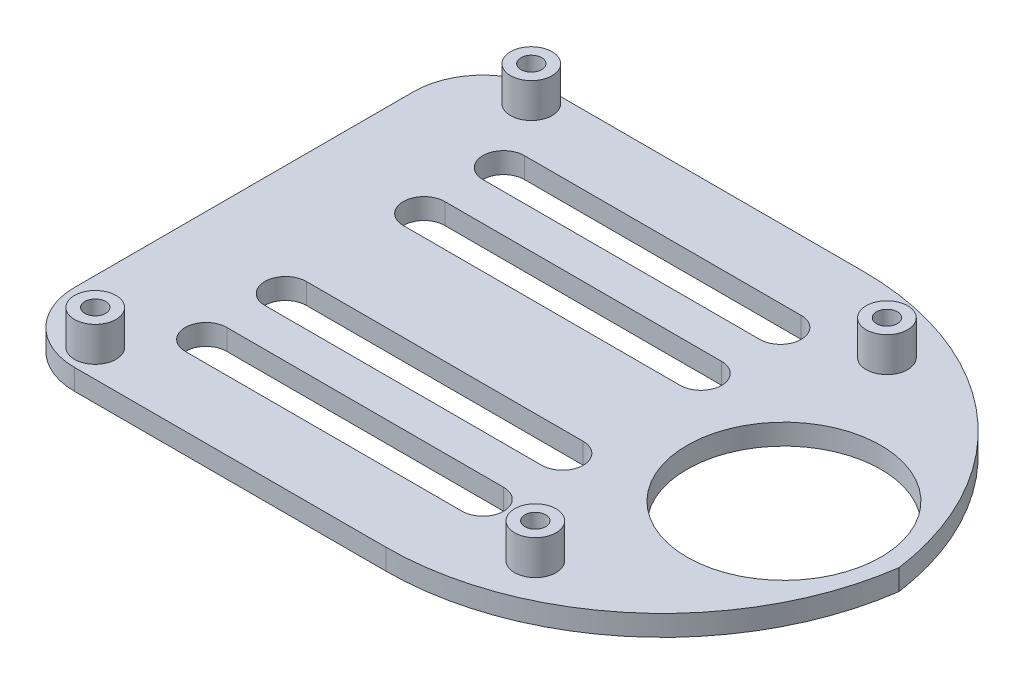
SolidWorks part; units mm, degrees
ref_plane "Plano frontal" through (0, 0, 0) normal (0, 0, 1) x (1, 0, 0)
ref_plane "Plano superior" through (0, 0, 0) normal (0, 1, 0) x (1, 0, 0)
ref_plane "Plano direito" through (0, 0, 0) normal (1, 0, 0) x (0, 0, -1)
sketch "Esboço1" plane through (0, 0, 0) normal (0, 1, 0) x (1, 0, 0)
  line L1 (-47.5, -34.5) -> (47.5, -34.5)
  line L2 (-47.5, -34.5) -> (-47.5, 34.5)
  line L3 (-47.5, 34.5) -> (47.5, 34.5)
  line L4 (47.5, -34.5) -> (47.5, 34.5)
  line L5 (-47.5, -34.5) -> (47.5, 34.5) construction
  line L6 (-47.5, 34.5) -> (47.5, -34.5) construction
  point P0 (0, 0)
  dimension "D1" = 95
  dimension "D2" = 69
extrude "Ressalto-extrusão1" add sketch "Esboço1" along normal blind 3
sketch "Esboço2" plane through (0, 3, 0) normal (0, 1, 0) x (1, 0, 0)
  line L0 (0, 0) -> (47.5, 0) construction
  line L1 (47.5, -34.5) -> (47.5, 34.5) construction
  circle A0 centre (30.5, 0) radius 14
  dimension "D1" = 28
  dimension "D2" = 17
extrude "Corte-extrusão1" cut sketch "Esboço2" against normal through all
sketch "Esboço4" plane through (0, 3, 0) normal (0, 1, 0) x (1, 0, 0)
  line L0 (-47.5, -34.5) -> (47.5, -34.5) construction
  line L1 (19.9772, 25.4) -> (19.9772, 34.5) construction
  line L2 (47.5, 0) -> (-47.5, 0) construction
  line L3 (47.5, -34.5) -> (47.5, 34.5) construction
  line L4 (-47.5, 34.5) -> (-47.5, -34.5) construction
  line L5 (-37.5, 31.5) -> (19.9772, 31.5) construction
  line L6 (-37.5, 31.5) -> (19.9772, 25.4) construction
  line L7 (47.5, 34.5) -> (-47.5, 34.5) construction
  circle A0 centre (19.9772, 25.4) radius 3 construction
  circle A3 centre (19.9772, 25.4) radius 1.5
  circle A4 centre (19.9772, -25.4) radius 1.5
  circle A5 centre (-37.5, 31.5) radius 1.5
  circle A6 centre (-38.5, -30.5) radius 1.5
  circle A7 centre (19.9772, -25.4) radius 3 construction
  circle A9 centre (-37.5, 31.5) radius 3 construction
  point P1 (0, 0)
  point P3 (0, 0)
  dimension "D1" = 50.8
  dimension "D2" = 3
  dimension "D3" = 3
  dimension "D4" = 3
  dimension "D6" = 6
  dimension "D7" = 6
  dimension "D8" = 57.8
  dimension "D9" = 6
  dimension "D10" = 3
  dimension "D11" = 3
  dimension "D5" = 10
  dimension "D12" = 9
  dimension "D13" = 4
extrude "Corte-extrusão2" cut sketch "Esboço4" against normal through all
sketch "Esboço5" plane through (0, 3, 0) normal (0, 1, 0) x (1, 0, 0)
  line L0 (47.5, 0) -> (-47.5, 0) construction
  line L1 (47.5, -34.5) -> (47.5, 34.5) construction
  line L2 (-47.5, 34.5) -> (-47.5, -34.5) construction
  circle A0 centre (-37.5, 31.5) radius 3
  circle A1 centre (-37.5, 31.5) radius 1.5
  circle A2 centre (19.9772, 25.4) radius 1.5
  circle A3 centre (19.9772, 25.4) radius 3
  circle A4 centre (19.9772, -25.4) radius 3
  circle A5 centre (19.9772, -25.4) radius 1.5
  circle A8 centre (-38.5, -30.5) radius 1.5
  circle A9 centre (-38.5, -30.5) radius 3
  dimension "D1" = 6
  dimension "D2" = 3
  dimension "D3" = 3
  dimension "D4" = 6
  dimension "D5" = 3
  dimension "D6" = 6
extrude "Ressalto-extrusão2" add sketch "Esboço5" along normal blind 5
fillet "Filete1" radius 40 2 edges at (47.5, 1.5, -34.5) (47.5, 1.5, 34.5)
fillet "Filete2" radius 10 2 edges at (-47.5, 1.5, 34.5) (-47.5, 1.5, -34.5)
sketch "Esboço7" plane through (0, 3, 0) normal (0, 1, 0) x (1, 0, 0)
  line L0 (16.5, 0) -> (-47.5, 0) construction
  line L1 (-47.5, 24.5) -> (-47.5, -24.5) construction
  line L2 (-31.5, 21.5) -> (8.5, 21.5) construction
  line L5 (-31.5, 10) -> (8.5, 10) construction
  line L6 (-31.5, 13) -> (8.5, 13)
  line L7 (-31.5, 7) -> (8.5, 7)
  line L8 (-31.5, 24.5) -> (8.5, 24.5)
  line L9 (-31.5, 18.5) -> (8.5, 18.5)
  line L10 (7.5, 34.5) -> (-37.5, 34.5) construction
  line L11 (-31.5, -21.5) -> (8.5, -21.5) construction
  line L12 (-31.5, -24.5) -> (8.5, -24.5)
  line L13 (-31.5, -18.5) -> (8.5, -18.5)
  line L14 (-31.5, -10) -> (8.5, -10) construction
  line L15 (-31.5, -13) -> (8.5, -13)
  line L16 (-31.5, -7) -> (8.5, -7)
  circle A0 centre (30.5, 0) radius 14 construction
  arc A3 (-31.5, 13) -> (-31.5, 7) centre (-31.5, 10) ccw
  arc A4 (8.5, 7) -> (8.5, 13) centre (8.5, 10) ccw
  arc A5 (-31.5, 24.5) -> (-31.5, 18.5) centre (-31.5, 21.5) ccw
  arc A6 (8.5, 18.5) -> (8.5, 24.5) centre (8.5, 21.5) ccw
  arc A7 (-31.5, -24.5) -> (-31.5, -18.5) centre (-31.5, -21.5) cw
  arc A8 (8.5, -18.5) -> (8.5, -24.5) centre (8.5, -21.5) cw
  arc A9 (-31.5, -13) -> (-31.5, -7) centre (-31.5, -10) cw
  arc A10 (8.5, -7) -> (8.5, -13) centre (8.5, -10) cw
  point P8 (-11.5, 21.5)
  point P15 (-11.5, 10)
  point P24 (-11.5, -21.5)
  point P31 (-11.5, -10)
  dimension "D5" = 16
  dimension "D1" = 10
  dimension "D2" = 3
  dimension "D3" = 40
  dimension "D4" = 7
  dimension "D6" = 16
extrude "Corte-extrusão3" cut sketch "Esboço7" against normal through all
